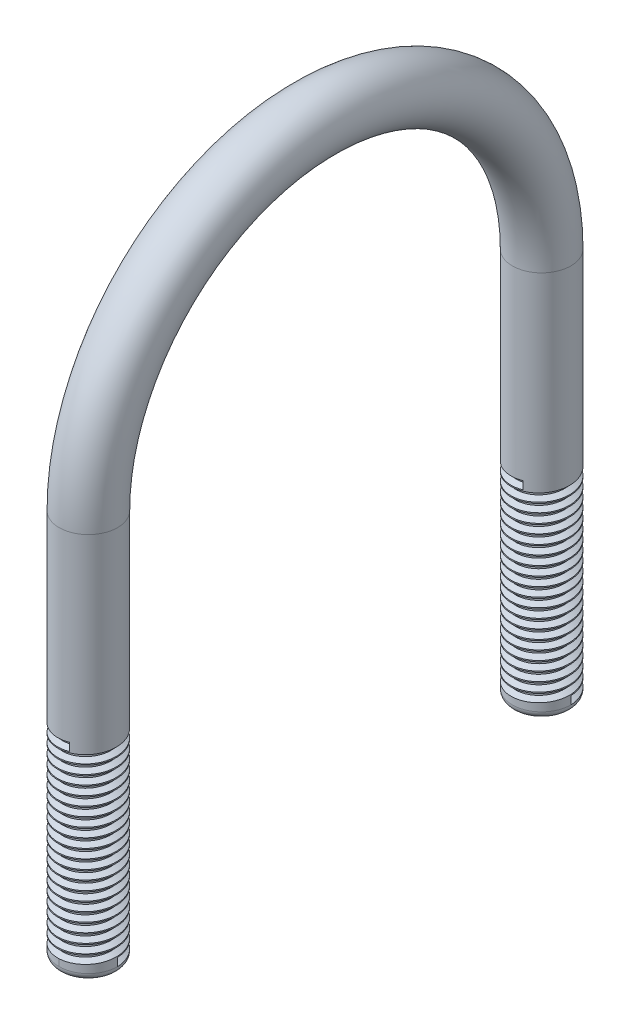
SolidWorks part; units mm, degrees
ref_plane "Спереди" through (0, 0, 0) normal (0, 0, 1) x (1, 0, 0)
ref_plane "Сверху" through (0, 0, 0) normal (0, 1, 0) x (1, 0, 0)
ref_plane "Справа" through (0, 0, 0) normal (1, 0, 0) x (0, 0, -1)
sketch "Эскиз1" plane through (0, 0, 0) normal (1, 0, 0) x (0, 0, -1)
  line L0 (-31, 53) -> (-31, 0)
  line L1 (31, 53) -> (31, 0)
  arc A0 (-31, 53) -> (31, 53) centre (0, 53) cw
  dimension "D1" = 31
  dimension "D2" = 53
  dimension "D3" = 53
  dimension "D4" = 53
  dimension "D5" = 31
sketch "Эскиз2" plane through (0, 0, 0) normal (0, 1, 0) x (1, 0, 0)
  line L0 (0, -31) -> (0, 31) construction
  circle A0 centre (0, 31) radius 4
  dimension "D1" = 8
  dimension "D2" = 31
sweep "По траектории1" add profiles "Эскиз2" path "Эскиз1"
fillet "Скругление1" radius 1 2 edges at (0, 0, -27) (0, 0, 27)
thread "Резьба1" pitch 1.25 method cut profile "Профиль резьбы1" start angle 0, offset 0, length 26, pitch 1.25, diameter 8
ref_plane "Плоскость1" through (4, 1, 31) normal (0, 0, 1) x (1, 0, 0)
sketch "Профиль резьбы1" plane through (4, 1, 31) normal (0, 0, 1) x (1, 0, 0)
  line L0 (0, 0) -> (0, 1.25) construction
  line L11 (0, 0) -> (0, 1.0937)
  line L12 (0, 1.0937) -> (-0.6766, 0.7031)
  line L13 (-0.6766, 0.7031) -> (-0.6766, 0.3906)
  line L15 (-0.6766, 0.3906) -> (0, 0)
  line L17 (-0.6766, 0.5469) -> (0, 0.5469) construction
  point P2 (0, 0)
  dimension "Pitch" = 1.25
  dimension "Profile_Angle" = 60
  dimension "Profile_Land" = 0.3125
  dimension "Profile_Height" = 0.6766
thread "Резьба2" pitch 1.25 method cut profile "Профиль резьбы2" start angle 0, offset 0, length 26, pitch 1.25, diameter 8
ref_plane "Плоскость2" through (4, 1, -31) normal (0, 0, 1) x (1, 0, 0)
sketch "Профиль резьбы2" plane through (4, 1, -31) normal (0, 0, 1) x (1, 0, 0)
  line L0 (0, 0) -> (0, 1.25) construction
  line L11 (0, 0) -> (0, 1.0937)
  line L12 (0, 1.0937) -> (-0.6766, 0.7031)
  line L13 (-0.6766, 0.7031) -> (-0.6766, 0.3906)
  line L15 (-0.6766, 0.3906) -> (0, 0)
  line L17 (-0.6766, 0.5469) -> (0, 0.5469) construction
  point P2 (0, 0)
  dimension "Pitch" = 1.25
  dimension "Profile_Angle" = 60
  dimension "Profile_Land" = 0.3125
  dimension "Profile_Height" = 0.6766
